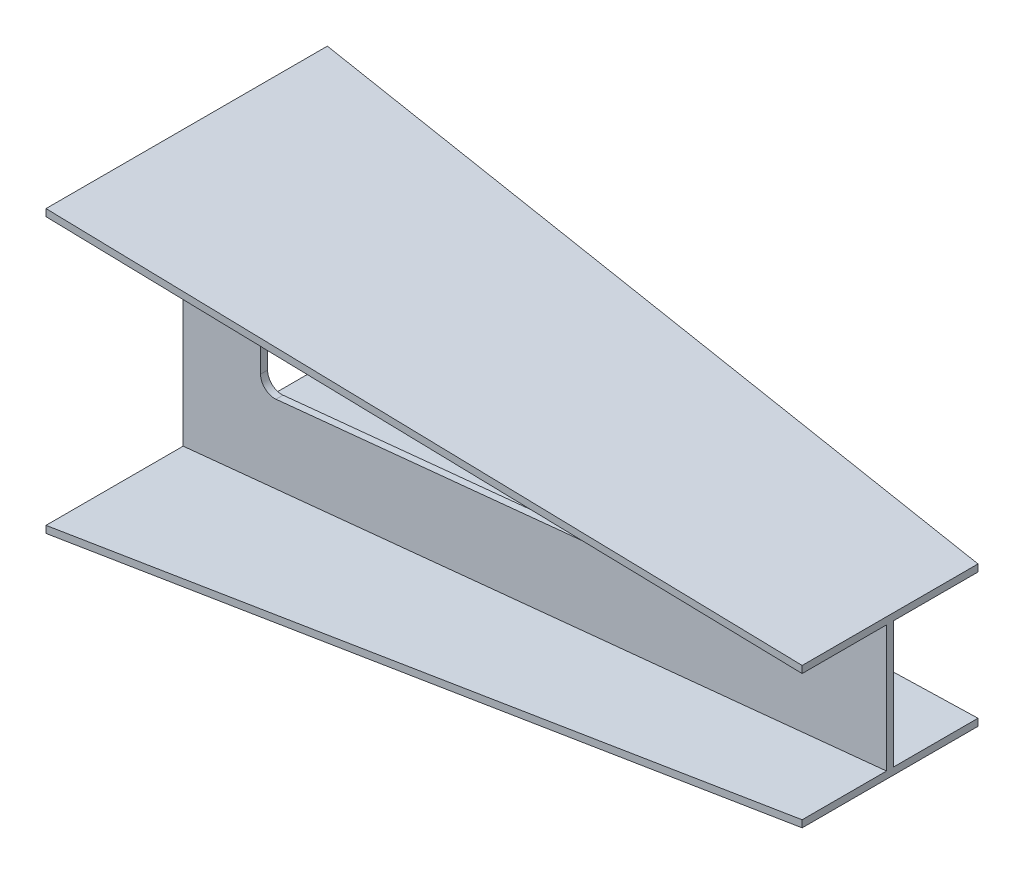
SolidWorks part; units mm, degrees
ref_plane "Front Plane" through (0, 0, 0) normal (0, 0, 1) x (1, 0, 0)
ref_plane "Top Plane" through (0, 0, 0) normal (0, 1, 0) x (1, 0, 0)
ref_plane "Right Plane" through (0, 0, 0) normal (1, 0, 0) x (0, 0, -1)
sketch "Sketch1" plane through (0, 0, 0) normal (1, 0, 0) x (0, 0, -1)
  line L1 (-205, 200) -> (195, 200)
  line L2 (-205, 200) -> (-205, 190)
  line L4 (195, 200) -> (195, 190)
  line L6 (-205, -190) -> (-205, -200)
  line L7 (-205, -200) -> (195, -200)
  line L8 (195, -190) -> (195, -200)
  line L15 (-205, -190) -> (-10, -190)
  line L16 (-5, 190) -> (-5, -790) construction
  line L18 (-205, 190) -> (-10, 190)
  line L19 (0, 0) -> (192.2403, 0) construction
  line L21 (-10, 190) -> (-10, -190)
  line L23 (0, 190) -> (0, -190)
  line L27 (0, 190) -> (195, 190)
  line L28 (0, -190) -> (195, -190)
  dimension "D1" = 400
  dimension "D2" = 10
  dimension "D3" = 400
  dimension "D4" = 10
ref_plane "Plane2" through (1000, 0, 0) normal (1, 0, 0) x (0, 0, -1)
sketch "Sketch4" plane through (1000, 0, -1000) normal (-1, 0, 0) x (0, 0, 1)
  line L1 (880, 100) -> (1130, 100)
  line L2 (880, 100) -> (880, 90)
  line L4 (1130, 100) -> (1130, 90)
  line L6 (880, -90) -> (880, -100)
  line L7 (880, -100) -> (1130, -100)
  line L8 (1130, -90) -> (1130, -100)
  line L15 (880, -90) -> (1000, -90)
  line L16 (1005, 390) -> (1005, -390) construction
  line L18 (880, 90) -> (1000, 90)
  line L19 (1010, -90) -> (1130, -90)
  line L21 (1000, 90) -> (1000, -90)
  line L23 (1010, 90) -> (1010, -90)
  line L24 (1010, 90) -> (1130, 90)
  line L26 (1010, 190) -> (1010, -190) construction
  line L27 (1000, 0) -> (820.2065, 0) construction
  dimension "D1" = 250
  dimension "D2" = 10
  dimension "D3" = 200
  dimension "D4" = 10
loft "Loft4" add profiles "Sketch1", "Sketch4" connector at (0, 190, 10) connector at (1000, 90, 10)
sketch "Sketch5" plane through (0, 0, 10) normal (0, 0, 1) x (1, 0, 0)
  line L8 (110, -68.4514) -> (794.5137, 0)
  line L9 (794.5137, 0) -> (110, 68.4514)
  line L10 (110, 68.4514) -> (110, -68.4514)
  line L11 (131.9901, -66.2524) -> (595.5062, -19.9007)
  line L12 (595.5062, 19.9007) -> (131.9901, 66.2524)
  line L13 (110, 46.3516) -> (110, -46.3516)
  arc A0 (595.5062, -19.9007) -> (595.5062, 19.9007) centre (593.5162, 0) ccw
  arc A1 (131.9901, -66.2524) -> (110, -46.3516) centre (130, -46.3516) cw
  arc A2 (131.9901, 66.2524) -> (110, 46.3516) centre (130, 46.3516) ccw
  dimension "D2" = 20
  dimension "D1" = 110
extrude "Cut-Extrude1" cut sketch "Sketch5" against normal through all
